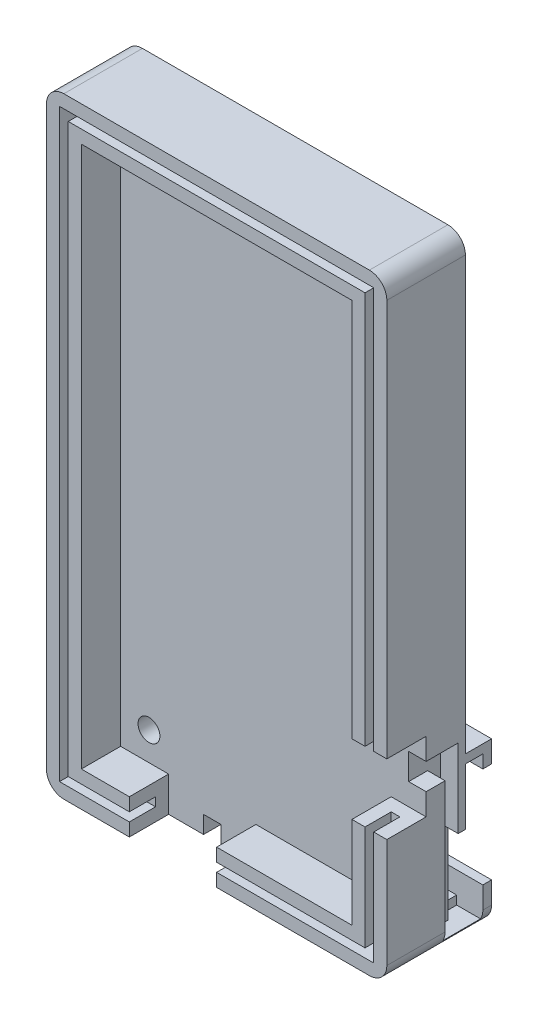
SolidWorks part; units mm, degrees
ref_plane "Front Plane" through (0, 0, 0) normal (0, 0, 1) x (1, 0, 0)
ref_plane "Top Plane" through (0, 0, 0) normal (0, 1, 0) x (1, 0, 0)
ref_plane "Right Plane" through (0, 0, 0) normal (1, 0, 0) x (0, 0, -1)
sketch "Sketch1" plane through (0, 0, 0) normal (0, 0, 1) x (1, 0, 0)
  line L1 (0, 0) -> (39, 0)
  line L2 (0, 0) -> (0, 70)
  line L3 (0, 70) -> (39, 70)
  line L4 (39, 0) -> (39, 70)
  dimension "D1" = 70
  dimension "D2" = 39
extrude "Boss-Extrude1" add sketch "Sketch1" along normal blind 4.5
sketch "Sketch2" plane through (0, 0, 4.5) normal (0, 0, 1) x (1, 0, 0)
  line L0 (0, 70) -> (0, 0) construction
  line L1 (39, 70) -> (0, 70)
  line L2 (39, 70) -> (39, 66)
  line L3 (39, 66) -> (0, 66)
  line L4 (0, 70) -> (0, 66)
  line L5 (0, 0) -> (39, 0) construction
  line L6 (0, 66) -> (4, 66)
  line L7 (0, 66) -> (0, 0)
  line L8 (0, 0) -> (4, 0)
  line L9 (4, 66) -> (4, 0)
  line L10 (39, 0) -> (39, 70) construction
  line L11 (4, 0) -> (39, 0)
  line L12 (4, 0) -> (4, 4)
  line L13 (4, 4) -> (39, 4)
  line L14 (39, 0) -> (39, 4)
  line L16 (39, 66) -> (35, 66)
  line L17 (39, 66) -> (39, 4)
  line L18 (39, 4) -> (35, 4)
  line L19 (35, 66) -> (35, 4)
  line M6 (0, 70) -> (0, 0)
  line M7 (0, 0) -> (39, 0)
  line M8 (39, 0) -> (39, 70)
  line M9 (39, 70) -> (0, 70)
  dimension "D1" = 4
  dimension "D2" = 4
  dimension "D3" = 4
  dimension "D4" = 4
extrude "Boss-Extrude2" add sketch "Sketch2" along normal blind 4.5 contours L3 M8 M9 M6 | L3 L19 L13 M8 | L9 L3 M6 M7 | L13 L9 M7 M8 region at (19.5, 68, 4.5) region at (37, 35, 4.5) region at (2, 33, 4.5) region at (21.5, 2, 4.5)
sketch "Sketch3" plane through (0, 4, 0) normal (0, 1, 0) x (1, 0, 0)
  line L0 (4, -4.5) -> (35, -4.5) construction
  line L1 (9.5, -4.5) -> (19.5, -4.5)
  line L2 (9.5, -4.5) -> (9.5, -9)
  line L3 (9.5, -9) -> (19.5, -9)
  line L4 (19.5, -4.5) -> (19.5, -9)
  line L5 (4, -9) -> (35, -9) construction
  line L6 (4, -9) -> (4, -4.5) construction
  dimension "D1" = 5.5
  dimension "D2" = 15.5
extrude "Cut-Extrude1" cut sketch "Sketch3" against normal blind 4
sketch "Sketch4" plane through (35, 0, 0) normal (-1, 0, 0) x (0, 0, 1)
  line L0 (4.5, 66) -> (4.5, 4) construction
  line L1 (4.5, 14.5) -> (9, 14.5)
  line L2 (4.5, 14.5) -> (4.5, 22.5)
  line L3 (4.5, 22.5) -> (9, 22.5)
  line L4 (9, 14.5) -> (9, 22.5)
  line L5 (9, 66) -> (9, 4) construction
  line L6 (9, 4) -> (4.5, 4) construction
  dimension "D1" = 10.5
  dimension "D2" = 18.5
extrude "Cut-Extrude2" cut sketch "Sketch4" against normal blind 4
sketch "Sketch5" plane through (0, 0, 4.5) normal (0, 0, 1) x (1, 0, 0)
  line L0 (4, 4) -> (9.5, 4) construction
  line L1 (4, 66) -> (4, 4) construction
  line L2 (19.5, 66) -> (19.5, 4) construction
  line L3 (35, 66) -> (4, 66) construction
  line L5 (19.5, 35) -> (4, 35) construction
  line L6 (4, 66) -> (4, 4) construction
  circle A0 centre (7.25, 7.25) radius 1.25
  circle A1 centre (31.75, 7.25) radius 1.25
  circle A2 centre (7.25, 62.75) radius 1.25
  dimension "D1" = 3.25
  dimension "D3" = 2.5
  dimension "D2" = 3.25
extrude "Cut-Extrude3" cut sketch "Sketch5" against normal blind 4
sketch "Sketch7" plane through (0, 0, 0) normal (0, 0, -1) x (-1, 0, 0)
  line L0 (-39, 0) -> (-39, 18.5) construction
  line L1 (-39, 0) -> (-39, 70) construction
  line L3 (-39, 1) -> (-8, 1)
  line L4 (-39, 1) -> (-39, 17.5)
  line L5 (-39, 17.5) -> (-8, 17.5)
  line L6 (-8, 1) -> (-8, 17.5)
  line L9 (0, 0) -> (-39, 0) construction
  line L10 (-39, 0) -> (-7, 0)
  line L11 (-7, 0) -> (-7, 18.5)
  line L12 (-7, 18.5) -> (-39, 18.5)
  line L13 (-39, 18.5) -> (-39, 17.5)
  line L14 (-39, 1) -> (-39, 0)
  line M8 (-39, 70) -> (-39, 0)
  line M9 (-39, 0) -> (0, 0)
  dimension "D1" = 18.5
  dimension "D2" = 1
  dimension "D3" = 16.5
  dimension "D4" = 31
  dimension "D5" = 32
  dimension "D6" = 18.5
extrude "Boss-Extrude3" add sketch "Sketch7" along normal blind 3 contours L11 L12 L5 L6 L3 M8 M9 region at (23.5, 0.6304, 0)
sketch "Sketch8" plane through (8, 0, 0) normal (1, 0, 0) x (0, 0, -1)
  line L0 (3, 17.5) -> (0, 17.5) construction
  line L1 (1, 17.5) -> (2, 17.5)
  line L2 (1, 17.5) -> (1, 16.5)
  line L3 (1, 16.5) -> (2, 16.5)
  line L4 (2, 17.5) -> (2, 16.5)
  line L5 (0, 1) -> (0, 17.5) construction
  line L6 (0, 9.25) -> (3, 9.25) construction
  line L7 (3, 1) -> (3, 17.5) construction
  line L8 (1, 2) -> (2, 2)
  line L9 (2, 1) -> (2, 2)
  line L10 (1, 1) -> (2, 1)
  line L11 (1, 1) -> (1, 2)
  dimension "D1" = 1
  dimension "D2" = 1
  dimension "D3" = 1
extrude "Boss-Extrude4" add sketch "Sketch8" along normal blind 28
sketch "Sketch9" plane through (8, 0, 0) normal (1, 0, 0) x (0, 0, -1)
  line L1 (3, 1) -> (2, 1)
  line L2 (3, 1) -> (3, 17.5)
  line L3 (3, 17.5) -> (2, 17.5)
  line L4 (2, 1) -> (2, 17.5)
extrude "Boss-Extrude5" add sketch "Sketch9" along normal blind 14
sketch "Sketch10" plane through (22, 0, 0) normal (1, 0, 0) x (0, 0, -1)
  line L0 (3, 1) -> (3, 17.5) construction
  line L1 (2, 17.5) -> (3, 17.5)
  line L2 (2, 17.5) -> (2, 16)
  line L3 (2, 16) -> (3, 16)
  line L4 (3, 17.5) -> (3, 16)
  line L6 (2, 1) -> (3, 1)
  line L7 (2, 1) -> (2, 4.5)
  line L8 (2, 4.5) -> (3, 4.5)
  line L9 (3, 1) -> (3, 4.5)
  dimension "D1" = 1.5
  dimension "D2" = 3.5
extrude "Boss-Extrude6" add sketch "Sketch10" along normal blind 17
sketch "Sketch11" plane through (0, 0, 0) normal (0, 0, -1) x (-1, 0, 0)
  line L0 (0, 0) -> (-7, 0) construction
  line L1 (-4, 0) -> (-5, 0)
  line L2 (-4, 0) -> (-4, 21.5)
  line L3 (-4, 21.5) -> (-5, 21.5)
  line L4 (-5, 0) -> (-5, 21.5)
  line L5 (-7, 0) -> (-7, 18.5) construction
  line L7 (0, 70) -> (0, 0) construction
  line L8 (-5, 21.5) -> (-22, 21.5)
  line L9 (-5, 21.5) -> (-5, 20.5)
  line L10 (-5, 20.5) -> (-22, 20.5)
  line L11 (-22, 21.5) -> (-22, 20.5)
  line L12 (-7, 18.5) -> (-39, 18.5) construction
  line L13 (-28, 18.5) -> (-27, 18.5)
  line L14 (-28, 18.5) -> (-28, 21.5)
  line L15 (-28, 21.5) -> (-27, 21.5)
  line L16 (-27, 18.5) -> (-27, 21.5)
  line M5 (-7, 0) -> (0, 0)
  line M9 (-39, 18.5) -> (-7, 18.5)
  dimension "D1" = 1
  dimension "D2" = 2
  dimension "D3" = 21.5
  dimension "D4" = 1
  dimension "D5" = 22
  dimension "D6" = 5
  dimension "D7" = 1
  dimension "D8" = 3
extrude "Boss-Extrude7" add sketch "Sketch11" along normal blind 3 contours L4 L2 L3 M5 | L8 L11 L10 L4 | L16 L15 L14 M9 region at (4.5, 10.75, 0) region at (13.5, 21, 0) region at (27.5, 20, 0)
sketch "Sketch12" plane through (0, 0, 0) normal (0, -1, 0) x (1, 0, 0)
  line L0 (19.5, 4.5) -> (9.5, 4.5) construction
  line L1 (5, 0) -> (15.5, 0)
  line L2 (5, 0) -> (5, 2)
  line L3 (5, 2) -> (15.5, 2)
  line L4 (15.5, 0) -> (15.5, 2)
  line L5 (9.5, 4.5) -> (9.5, 9) construction
  line L6 (13.5, 4.5) -> (15.5, 4.5)
  line L7 (13.5, 4.5) -> (13.5, 2)
  line L8 (13.5, 2) -> (15.5, 2)
  line L9 (15.5, 4.5) -> (15.5, 2)
  line L10 (19.5, 9) -> (19.5, 4.5) construction
  line M5 (19.5, 4.5) -> (9.5, 4.5)
  line M13 (5, 0) -> (7, 0)
  dimension "D1" = 2
  dimension "D2" = 4
  dimension "D3" = 4
  dimension "D4" = 0
extrude "Cut-Extrude4" cut sketch "Sketch12" against normal blind 2 contours L1 L4 L3 L2 M13 | L9 L7 L3 M5 region at (10.25, 0, 1) region at (14.5, 0, 3.25)
sketch "Sketch13" plane through (39, 0, 0) normal (1, 0, 0) x (0, 0, -1)
  line L0 (-4.5, 22.5) -> (-4.5, 14.5) construction
  line L1 (-4.5, 20) -> (-2.3266, 20)
  line L2 (-4.5, 20) -> (-4.5, 17)
  line L3 (-4.5, 17) -> (-2.3266, 17)
  line L4 (-2.3266, 20) -> (-2.3266, 17)
  line L5 (-9, 22.5) -> (-4.5, 22.5) construction
  line L6 (-4.5, 14.5) -> (-9, 14.5) construction
  line L7 (-2.3266, 17) -> (-2.3266, 11)
  line L8 (0, 1) -> (-2.3266, 1)
  line L9 (0, 1) -> (0, 11)
  line L10 (0, 11) -> (-2.3266, 11)
  line L11 (-2.3266, 1) -> (-2.3266, 11)
  line L18 (-2.3266, 11) -> (-0.8266, 11)
  line L19 (-2.3266, 11) -> (-2.3266, 20)
  line L20 (-2.3266, 20) -> (-0.8266, 20)
  line L21 (-0.8266, 11) -> (-0.8266, 20)
  line M19 (-4.5, 22.5) -> (-4.5, 14.5)
  line M27 (0, 1) -> (0, 17.5)
  dimension "D1" = 2.5
  dimension "D2" = 2.5
  dimension "D3" = 10
  dimension "D4" = 1.5
  dimension "D5" = 2.3266
extrude "Cut-Extrude5" cut sketch "Sketch13" against normal blind 2 contours L4 L1 L3 M19 | L10 L21 L20 L4 L7 | L11 L8 L10 M27 region at (39, 18.5, 3.4133) region at (39, 15.5, 1.5766) region at (39, 6, 1.1633)
sketch "Sketch14" plane through (0, 0, 9) normal (0, 0, 1) x (1, 0, 0)
  line L1 (1.5, 1.5) -> (2.5, 1.5)
  line L2 (1.5, 1.5) -> (1.5, 68.5)
  line L3 (1.5, 68.5) -> (2.5, 68.5)
  line L4 (2.5, 1.5) -> (2.5, 68.5)
  line L5 (0, 70) -> (0, 0) construction
  line L6 (4, 66) -> (4, 4) construction
  line L7 (39, 70) -> (0, 70) construction
  line L8 (35, 66) -> (4, 66) construction
  line L9 (2.5, 68.5) -> (37.5, 68.5)
  line L10 (2.5, 68.5) -> (2.5, 67.5)
  line L11 (2.5, 67.5) -> (37.5, 67.5)
  line L12 (37.5, 68.5) -> (37.5, 67.5)
  line L13 (39, 22.5) -> (39, 70) construction
  line L14 (19.5, 70) -> (19.5, 0) construction
  line L15 (0, 35) -> (39, 35) construction
  line L16 (37.5, 68.5) -> (36.5, 68.5)
  line L17 (36.5, 1.5) -> (36.5, 68.5)
  line L18 (37.5, 1.5) -> (36.5, 1.5)
  line L19 (37.5, 1.5) -> (37.5, 68.5)
  line L20 (2.5, 2.5) -> (37.5, 2.5)
  line L21 (37.5, 1.5) -> (37.5, 2.5)
  line L22 (2.5, 1.5) -> (37.5, 1.5)
  line L23 (2.5, 1.5) -> (2.5, 2.5)
  line M15 (35, 22.5) -> (39, 22.5)
  line M20 (9.5, 0) -> (9.5, 4)
  dimension "D2" = 1.5
  dimension "D3" = 1.5
  dimension "D4" = 1.5
  dimension "D5" = 1.5
extrude "Cut-Extrude6" cut sketch "Sketch14" against normal blind 3 contours L1 L4 L3 L2 | L4 L22 L20 M20 | L22 L17 L20 M20 | L20 L17 L18 L19 | L17 L20 L19 M15 | L19 L11 L17 M15 | L11 L17 L9 L4 | L17 L11 L12 L9 region at (2, 35, 9) region at (6, 2, 9) region at (23, 2, 9) region at (19.5, 68, 9) region at (37, 2, 9) region at (37, 68, 9) region at (37, 45, 9) region at (37, 12.5, 9)
fillet "Fillet2" radius 2 4 edges at (0, 0, 4.5) (0, 70, 4.5) (39, 70, 4.5) (39, 0, 3)
